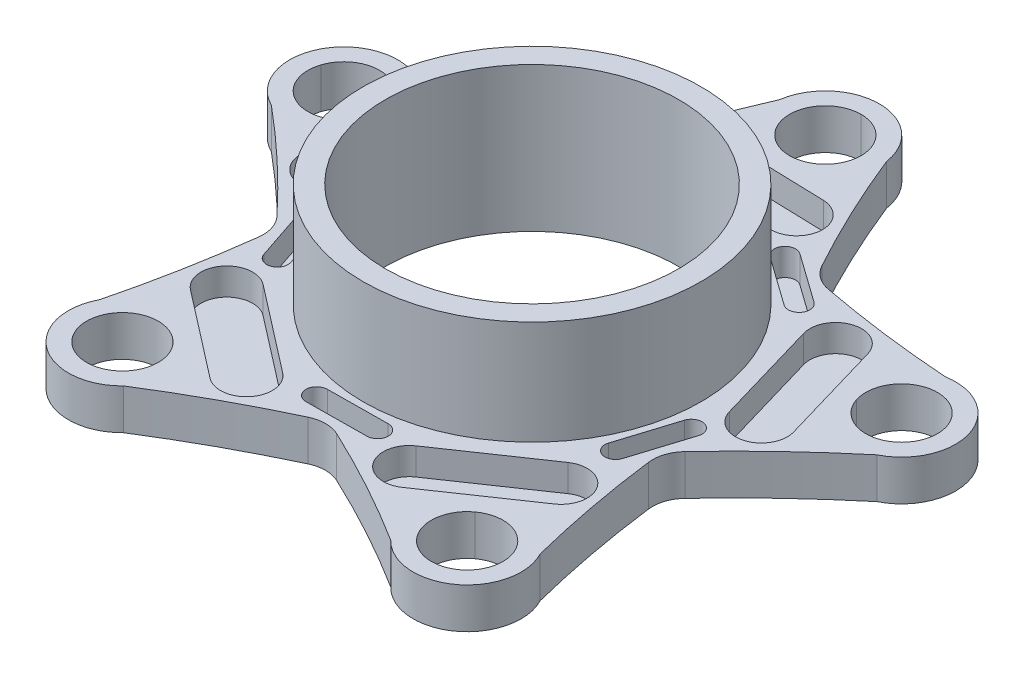
SolidWorks part; units mm, degrees
ref_plane "Front Plane" through (0, 0, 0) normal (0, 0, 1) x (1, 0, 0)
ref_plane "Top Plane" through (0, 0, 0) normal (0, 1, 0) x (1, 0, 0)
ref_plane "Right Plane" through (0, 0, 0) normal (1, 0, 0) x (0, 0, -1)
sketch "Sketch1" plane through (0, 0, 0) normal (0, 1, 0) x (1, 0, 0)
  circle A0 centre (0, 0) radius 31.75
  dimension "D1" = 63.5
extrude "CenterCircleExtrude" add sketch "Sketch1" along normal blind 19.558 contours A0
sketch "Sketch2" plane through (0, 0, 0) normal (0, -1, 0) x (1, 0, 0)
  circle A0 centre (0, 0) radius 80.01
  dimension "D1" = 160.02
extrude "BaseExpand" add sketch "Sketch2" along normal blind 7.62
sketch "Sketch3" plane through (0, 19.558, 0) normal (0, 1, 0) x (1, 0, 0)
  circle A0 centre (0, 0) radius 27.559
  dimension "D1" = 55.118
extrude "CenterCut" cut sketch "Sketch3" against normal blind 27.178 contours A0
sketch "Sketch4" plane through (0, 0, 0) normal (0, 1, 0) x (1, 0, 0)
  line L0 (-52.4203, 17.0324) -> (0, 55.118) construction
  line L1 (-26.2102, 36.0752) -> (-18.6622, 25.6863) construction
  circle A0 centre (0, 55.118) radius 6.731
  circle A1 centre (52.4203, 17.0324) radius 6.731
  circle A2 centre (32.3975, -44.5914) radius 6.731
  circle A3 centre (-32.3975, -44.5914) radius 6.731
  circle A4 centre (-52.4203, 17.0324) radius 6.731
  circle A5 centre (0, 0) radius 31.75 construction
  point P14 (0, 0)
  dimension "D1" = 13.462
  dimension "D2" = 55.118
  dimension "D3" = 5
extrude "OuterCircleCut" cut sketch "Sketch4" against normal blind 7.62
sketch "Sketch8" plane through (0, 0, 0) normal (0, 1, 0) x (1, 0, 0)
  line L0 (-52.4203, 17.0324) -> (0, 55.118) construction
  line L1 (-26.2102, 36.0752) -> (-18.6622, 25.6863) construction
  line L2 (26.2102, 36.0752) -> (18.6622, 25.6863) construction
  line L3 (42.4089, -13.7795) -> (30.196, -9.8113) construction
  line L4 (0, -44.5914) -> (0, -31.75) construction
  line L5 (-42.4089, -13.7795) -> (-30.196, -9.8113) construction
  line L6 (0, -14.9479) -> (0, 14.9479) construction
  line L8 (0, 0) -> (10.16, 55.118) construction
  line L9 (10.16, 55.118) -> (-10.16, 55.118) construction
  circle A0 centre (-52.4203, 17.0324) radius 10.16
  circle A1 centre (0, 55.118) radius 10.16
  circle A2 centre (52.4203, 17.0324) radius 10.16
  circle A3 centre (32.3975, -44.5914) radius 10.16
  circle A4 centre (-32.3975, -44.5914) radius 10.16
  circle A5 centre (0, 0) radius 31.75 construction
  arc A6 (22.4362, 30.8807) -> (8.4002, 60.8331) centre (204.9622, 134.6791) cw
  arc A7 (-22.4362, 30.8807) -> (-8.4002, 60.8331) centre (-204.9622, 134.6791) ccw
  arc A8 (22.4362, 30.8807) -> (55.2599, 26.7875) centre (64.7506, 236.5488) ccw
  arc A9 (36.3025, -11.7954) -> (60.4515, 10.8094) centre (191.4243, -153.3125) cw
  arc A10 (36.3025, -11.7954) -> (42.5527, -44.2774) centre (244.9803, 11.5161) ccw
  arc A11 (0, -38.1707) -> (28.9609, -54.1525) centre (-86.6555, -229.4315) cw
  arc A12 (0, -38.1707) -> (-28.9609, -54.1525) centre (86.6555, -229.4315) ccw
  arc A13 (-36.3025, -11.7954) -> (-42.5527, -44.2774) centre (-244.9803, 11.5161) cw
  arc A14 (-36.3025, -11.7954) -> (-60.4515, 10.8094) centre (-191.4243, -153.3125) ccw
  arc A15 (-22.4362, 30.8807) -> (-55.2599, 26.7875) centre (-64.7506, 236.5488) cw
  point P14 (0, 0)
  point P27 (0, 0)
  point P63 (0, 0)
  point P72 (0, 0)
  circle M12 centre (0, 0) radius 80.01
  dimension "D1" = 5
  dimension "D3" = 5
  dimension "D2" = 5
extrude "StarfishCut" cut sketch "Sketch8" against normal blind 7.62 contours A0 A1 A2 A3 A4 M12 region at (-77.747, 0, 0)
sketch "Sketch14" plane through (0, 0, 0) normal (0, 1, 0) x (1, 0, 0)
  line L0 (-35.0288, -5.7028) -> (-31.4189, -16.4524) construction
  line L4 (-31.5013, -25.8769) -> (-15.2419, -38.4471) construction
  line L6 (-33.12, -5.0618) -> (-29.5101, -15.8114)
  line L7 (-36.9376, -6.3438) -> (-33.3277, -17.0934)
  line L8 (-16.2482, 31.5521) -> (-25.3562, 24.7971) construction
  line L9 (-15.0487, 29.9349) -> (-24.1567, 23.1798)
  line L10 (-17.4477, 33.1694) -> (-26.5556, 26.4144)
  line L11 (24.9869, 25.2031) -> (15.748, 31.7779) construction
  line L12 (23.8194, 23.5625) -> (14.5805, 30.1373)
  line L13 (26.1544, 26.8436) -> (16.9154, 33.4184)
  line L14 (31.6909, -15.9758) -> (35.0889, -5.1573) construction
  line L15 (29.7699, -15.3724) -> (33.1679, -4.5539)
  line L16 (33.612, -16.5792) -> (37.01, -5.7607)
  line L17 (-5.4008, -35.0767) -> (5.9382, -34.9653) construction
  line L18 (-5.4206, -33.0632) -> (5.9184, -32.9518)
  line L19 (-5.3811, -37.0901) -> (5.958, -36.9787)
  line L20 (-28.5253, -22.0275) -> (-12.2659, -34.5977)
  line L23 (-34.4773, -29.7263) -> (-18.2178, -42.2965)
  line L24 (-34.3448, 21.9631) -> (-41.2754, 2.6151) construction
  line L25 (-29.7642, 20.3223) -> (-36.6948, 0.9743)
  line L26 (-38.9254, 23.6039) -> (-45.856, 4.2558)
  line L27 (10.275, 39.4508) -> (-10.2677, 40.0633) construction
  line L28 (10.13, 34.5874) -> (-10.4127, 35.1999)
  line L29 (10.42, 44.3143) -> (-10.1227, 44.9268)
  line L30 (40.6951, 2.4188) -> (34.9296, 22.1454) construction
  line L31 (36.0249, 1.0539) -> (30.2593, 20.7805)
  line L32 (45.3654, 3.7838) -> (39.5998, 23.5104)
  line L33 (14.8759, -37.9559) -> (31.8554, -26.3767) construction
  line L34 (12.1346, -33.9361) -> (29.114, -22.3568)
  line L35 (17.6173, -41.9757) -> (34.5967, -30.3965)
  arc A43 (-33.12, -5.0618) -> (-36.9376, -6.3438) centre (-35.0288, -5.7028) ccw
  arc A44 (-33.3277, -17.0934) -> (-29.5101, -15.8114) centre (-31.4189, -16.4524) ccw
  arc A64 (-15.0487, 29.9349) -> (-17.4477, 33.1694) centre (-16.2482, 31.5521) ccw
  arc A65 (-26.5556, 26.4144) -> (-24.1567, 23.1798) centre (-25.3562, 24.7971) ccw
  arc A66 (23.8194, 23.5625) -> (26.1544, 26.8436) centre (24.9869, 25.2031) ccw
  arc A67 (16.9154, 33.4184) -> (14.5805, 30.1373) centre (15.748, 31.7779) ccw
  arc A68 (29.7699, -15.3724) -> (33.612, -16.5792) centre (31.6909, -15.9758) ccw
  arc A69 (37.01, -5.7607) -> (33.1679, -4.5539) centre (35.0889, -5.1573) ccw
  arc A70 (-5.4206, -33.0632) -> (-5.3811, -37.0901) centre (-5.4008, -35.0767) ccw
  arc A71 (5.958, -36.9787) -> (5.9184, -32.9518) centre (5.9382, -34.9653) ccw
  arc A74 (-28.5253, -22.0275) -> (-34.4773, -29.7263) centre (-31.5013, -25.8769) ccw
  arc A75 (-18.2178, -42.2965) -> (-12.2659, -34.5977) centre (-15.2419, -38.4471) ccw
  arc A76 (-29.7642, 20.3223) -> (-38.9254, 23.6039) centre (-34.3448, 21.9631) ccw
  arc A77 (-45.856, 4.2558) -> (-36.6948, 0.9743) centre (-41.2754, 2.6151) ccw
  arc A78 (10.13, 34.5874) -> (10.42, 44.3143) centre (10.275, 39.4508) ccw
  arc A79 (-10.1227, 44.9268) -> (-10.4127, 35.1999) centre (-10.2677, 40.0633) ccw
  arc A80 (36.0249, 1.0539) -> (45.3654, 3.7838) centre (40.6951, 2.4188) ccw
  arc A81 (39.5998, 23.5104) -> (30.2593, 20.7805) centre (34.9296, 22.1454) ccw
  arc A82 (12.1346, -33.9361) -> (17.6173, -41.9757) centre (14.8759, -37.9559) ccw
  arc A83 (34.5967, -30.3965) -> (29.114, -22.3568) centre (31.8554, -26.3767) ccw
  point P2 (-33.2239, -11.0776)
  point P5 (-23.3716, -32.162)
  point P15 (-37.8101, 12.2891)
  point P22 (0.0037, 39.7571)
  point P29 (37.8123, 12.2821)
  point P34 (0, 0)
  point P37 (23.3657, -32.1663)
  point P42 (0, 0)
  point P51 (0.0346, -0.0647)
  point P61 (0, 0)
  point P67 (-20.8022, 28.1746)
  point P74 (20.3674, 28.4905)
  point P81 (33.3899, -10.5665)
  point P88 (0.2687, -35.021)
  point P93 (0, 0)
  point P97 (0, 0)
  dimension "D1" = 5
  dimension "D5" = 5
extrude "Batman Cut" cut sketch "Sketch14" against normal blind 5.08
ref_axis "Axis1" through (0, -7.62, 0) along (0, 1, 0)
fillet "Fillet12" radius 6.35 5 edges at (-36.3025, -3.81, 11.7954) (0, -3.81, 38.1707) (36.3025, -3.81, 11.7954) (22.4362, -3.81, -30.8807) (-22.4362, -3.81, -30.8807)
ref_plane "Plane1" through (0, 0, 0) normal (-0.309, 0, 0.9511) x (0.9511, 0, 0.309)
ref_plane "Plane2" through (0, 0, 0) normal (-0.809, 0, -0.5878) x (-0.5878, 0, 0.809)
ref_plane "Plane3" through (0, 0, 0) normal (-0.809, 0, 0.5878) x (0.5878, 0, 0.809)
ref_plane "Plane4" through (0, 0, 0) normal (0.309, 0, 0.9511) x (0.9511, 0, -0.309)
split line "Split Line1"
split line "Split Line2"
split line "Split Line3"
split line "Split Line4"
split line "Split Line5"
